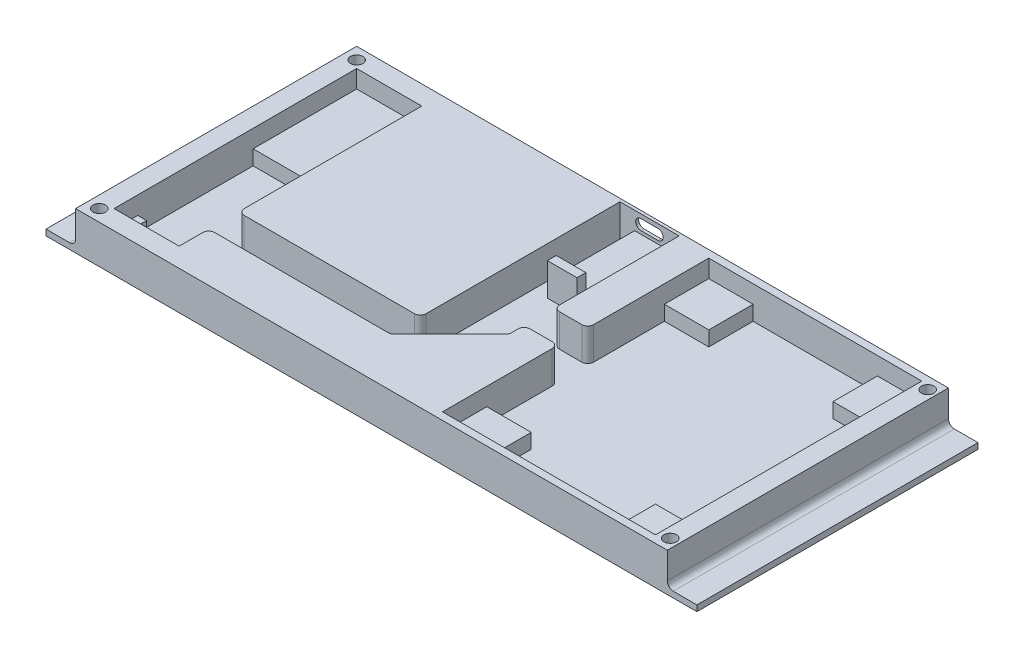
SolidWorks part; units mm, degrees
ref_plane "Front Plane" through (0, 0, 0) normal (0, 0, 1) x (1, 0, 0)
ref_plane "Top Plane" through (0, 0, 0) normal (0, 1, 0) x (1, 0, 0)
ref_plane "Right Plane" through (0, 0, 0) normal (1, 0, 0) x (0, 0, -1)
sketch "Sketch2" plane through (0, 0, 0) normal (0, 1, 0) x (1, 0, 0)
  line L0 (0, 0) -> (-50000, 0) construction
  line L1 (-100, 47.5) -> (100, 47.5)
  line L2 (-100, 47.5) -> (-100, -47.5)
  line L3 (-100, -47.5) -> (100, -47.5)
  line L4 (100, 47.5) -> (100, -47.5)
  line L5 (-100, 47.5) -> (100, -47.5) construction
  line L6 (-100, -47.5) -> (100, 47.5) construction
  line L7 (21.5, 45) -> (93.5, 45)
  line L8 (21.5, 45) -> (21.5, -45)
  line L9 (21.5, -45) -> (93.5, -45)
  line L10 (93.5, 45) -> (93.5, -45)
  line L11 (21.5, 45) -> (93.5, -45) construction
  line L12 (21.5, -45) -> (93.5, 45) construction
  line L13 (-93.5, 41) -> (-71.5, 41)
  line L14 (-93.5, 41) -> (-93.5, -41)
  line L15 (-93.5, -41) -> (-71.5, -41)
  line L16 (-71.5, 41) -> (-71.5, -41)
  line L17 (-93.5, 41) -> (-71.5, -41) construction
  line L18 (-93.5, -41) -> (-71.5, 41) construction
  line L19 (0, 0) -> (0, -50000) construction
  line L20 (-10, 46.5) -> (10, 46.5)
  line L21 (-10, 46.5) -> (-10, 22.5)
  line L22 (-10, 22.5) -> (10, 22.5)
  line L23 (10, 46.5) -> (10, 22.5)
  line L24 (-10, 46.5) -> (10, 22.5) construction
  line L25 (-10, 22.5) -> (10, 46.5) construction
  line L26 (-10, -31) -> (10, -11)
  line L27 (-71.5, -21) -> (-10, -21)
  line L28 (-71.5, -21) -> (-71.5, -31)
  line L29 (-71.5, -31) -> (-10, -31)
  line L30 (-10, -21) -> (-10, -31)
  line L31 (21.5, 4.0911) -> (10, 4.0911)
  line L32 (21.5, 4.0911) -> (21.5, -5.9089)
  line L33 (21.5, -5.9089) -> (10, -5.9089)
  line L34 (10, 4.0911) -> (10, -5.9089)
  line L35 (10, 22.5) -> (10, -11)
  line L37 (-10, 22.5) -> (-10, -31)
  point P0 (0, 0)
  point P6 (57.5, 0)
  point P12 (-82.5, 0)
  point P20 (0, 34.5)
  point P33 (0, 0)
  dimension "D1" = 200
  dimension "D2" = 90
  dimension "D3" = 72
  dimension "D4" = 95
  dimension "D5" = 82
  dimension "D6" = 22
  dimension "D7" = 6.5
  dimension "D8" = 6.5
  dimension "D9" = 20
  dimension "D10" = 24
  dimension "D11" = 1
  dimension "D12" = 10
  dimension "D13" = 10
  dimension "D14" = 10
extrude "Boss-Extrude1" add sketch "Sketch2" along normal blind 11 contours L4 L1 L2 L3 L37 L21 L20 L23 L35 L31 L8 L7 L10 L9 L33 L26 L29 L16 L15 L14 L13 L27 region at (-23.1419, 0, 0.0909)
sketch "Sketch3" plane through (0, 0, 0) normal (0, -1, 0) x (1, 0, 0)
  line L1 (-100, 47.5) -> (100, 47.5)
  line L2 (-100, 47.5) -> (-100, -47.5)
  line L3 (-100, -47.5) -> (100, -47.5)
  line L4 (100, 47.5) -> (100, -47.5)
extrude "Boss-Extrude2" add sketch "Sketch3" along normal blind 2
sketch "Sketch4" plane through (0, 0, 0) normal (0, 1, 0) x (1, 0, 0)
  line L0 (-71.5, 41) -> (-71.5, -21) construction
  line L1 (-93.5, 41) -> (-71.5, 41)
  line L2 (-93.5, 41) -> (-93.5, 6)
  line L3 (-93.5, 6) -> (-71.5, 6)
  line L4 (-71.5, 41) -> (-71.5, 6)
  line L5 (-5.0462, 46.5) -> (4.9538, 46.5)
  line L6 (-93.5, -41) -> (-90.5, -41)
  line L7 (-93.5, -41) -> (-93.5, -33)
  line L8 (-93.5, -33) -> (-90.5, -33)
  line L9 (-90.5, -41) -> (-90.5, -33)
  line L10 (21.5, 45) -> (36.5, 45)
  line L11 (21.5, 45) -> (21.5, 30)
  line L12 (21.5, 30) -> (36.5, 30)
  line L13 (36.5, 45) -> (36.5, 30)
  line L14 (93.5, 45) -> (78.5, 45)
  line L15 (93.5, 45) -> (93.5, 30)
  line L16 (93.5, 30) -> (78.5, 30)
  line L17 (78.5, 45) -> (78.5, 30)
  line L18 (93.5, -45) -> (78.5, -45)
  line L19 (93.5, -45) -> (93.5, -30)
  line L20 (93.5, -30) -> (78.5, -30)
  line L21 (78.5, -45) -> (78.5, -30)
  line L22 (21.5, -45) -> (36.5, -45)
  line L23 (21.5, -45) -> (21.5, -30)
  line L24 (21.5, -30) -> (36.5, -30)
  line L25 (36.5, -45) -> (36.5, -30)
  line L26 (-10, 46.5) -> (10, 46.5) construction
  line L27 (4.9538, 46.5) -> (4.9538, 20)
  line L28 (4.9538, 20) -> (-5.0462, 20)
  line L29 (-5.0462, 20) -> (-5.0462, 46.5)
  point P37 (-0.0462, 46.5)
  dimension "D1" = 35
  dimension "D2" = 8
  dimension "D3" = 3
  dimension "D4" = 15
  dimension "D5" = 15
  dimension "D6" = 15
  dimension "D7" = 15
  dimension "D8" = 10
  dimension "D9" = 26.5
extrude "Boss-Extrude3" add sketch "Sketch4" along normal blind 5
sketch "Sketch5" plane through (0, 0, -46.5) normal (0, 0, 1) x (1, 0, 0)
  line L0 (4.9538, 5) -> (-5.0462, 5) construction
  line L5 (-2.9462, 7.85) -> (2.8538, 7.85) construction
  line L6 (-2.9462, 9.6) -> (2.8538, 9.6)
  line L7 (-0.0462, 5) -> (-0.0462, 7.85)
  line L8 (-2.9462, 6.1) -> (2.8538, 6.1)
  arc A0 (-2.9462, 9.6) -> (-2.9462, 6.1) centre (-2.9462, 7.85) ccw
  arc A1 (2.8538, 6.1) -> (2.8538, 9.6) centre (2.8538, 7.85) ccw
  point P0 (-0.0462, 7.85)
  point P3 (-0.0462, 7.85)
  dimension "D2" = 9.3
  dimension "D1" = 3.5
  dimension "D3" = 1.1
extrude "Cut-Extrude1" cut sketch "Sketch5" against normal blind 7 contours L8 A1 L6 A0 region at (-0.0462, 9.5006, -46.5)
sketch "Sketch7" plane through (0, -2, 0) normal (0, -1, 0) x (1, 0, 0)
  line L0 (-100, -47.5) -> (100, -47.5) construction
  line L1 (-110, 47.5) -> (110, 47.5)
  line L2 (-110, 47.5) -> (-110, -47.5)
  line L3 (-110, -47.5) -> (110, -47.5)
  line L4 (110, 47.5) -> (110, -47.5)
  line L5 (-110, 47.5) -> (110, -47.5) construction
  line L6 (-110, -47.5) -> (110, 47.5) construction
  line L7 (-100, 47.5) -> (-100, -47.5) construction
  point P0 (0, 0)
  point P7 (120, -47.5)
  point P8 (137.675, -44.1885)
  dimension "D1" = 10
sketch "Sketch9" plane through (0, 0, 0) normal (0, 1, 0) x (1, 0, 0)
  line L0 (4.9538, 20) -> (4.9538, 46.5) construction
  line L1 (-5.0462, 20) -> (4.9538, 20)
  line L2 (-5.0462, 20) -> (-5.0462, 17)
  line L3 (-5.0462, 17) -> (4.9538, 17)
  line L4 (4.9538, 20) -> (4.9538, 17)
  dimension "D1" = 3
ref_plane "Plane1" through (4.9538, 0, -20) normal (0, 0, -1) x (-1, 0, 0)
extrude "Boss-Extrude4" add sketch "Sketch9" along normal up to surface (11 mm away) up to face at (-10, 11, 1.3492)
extrude "Boss-Extrude5" add sketch "Sketch7" against normal blind 2
fillet "Fillet1" radius 2 2 edges at (-100, 0, 0) (100, 0, 0)
fillet "Fillet2" radius 2 9 edges at (-10, 5.5, 31) (21.5, 5.5, 5.9089) (21.5, 5.5, -4.0911) (10, 5.5, -4.0911) (10, 5.5, 5.9089) (10, 5.5, 11) (-71.5, 5.5, 31) (-71.5, 5.5, 21) (-10, 5.5, 21)
sketch "Sketch10" plane through (0, 11, 0) normal (0, 1, 0) x (1, 0, 0)
  line L0 (-100, 47.5) -> (-100, -47.5) construction
  line L1 (-100, 47.5) -> (100, 47.5) construction
  line L2 (-100, -47.5) -> (100, -47.5) construction
  line L3 (100, 47.5) -> (100, -47.5) construction
  circle A0 centre (-96, 43.5) radius 2.1
  circle A1 centre (-96, -43.5) radius 2.1
  circle A2 centre (97, -43.5) radius 2.1
  circle A3 centre (97, 43.5) radius 2.1
  dimension "D1" = 4.2
  dimension "D2" = 4
  dimension "D3" = 4
  dimension "D4" = 4
  dimension "D5" = 4
  dimension "D6" = 3
  dimension "D7" = 4
  dimension "D8" = 3
  dimension "D9" = 4
extrude "Cut-Extrude2" cut sketch "Sketch10" against normal blind 6
